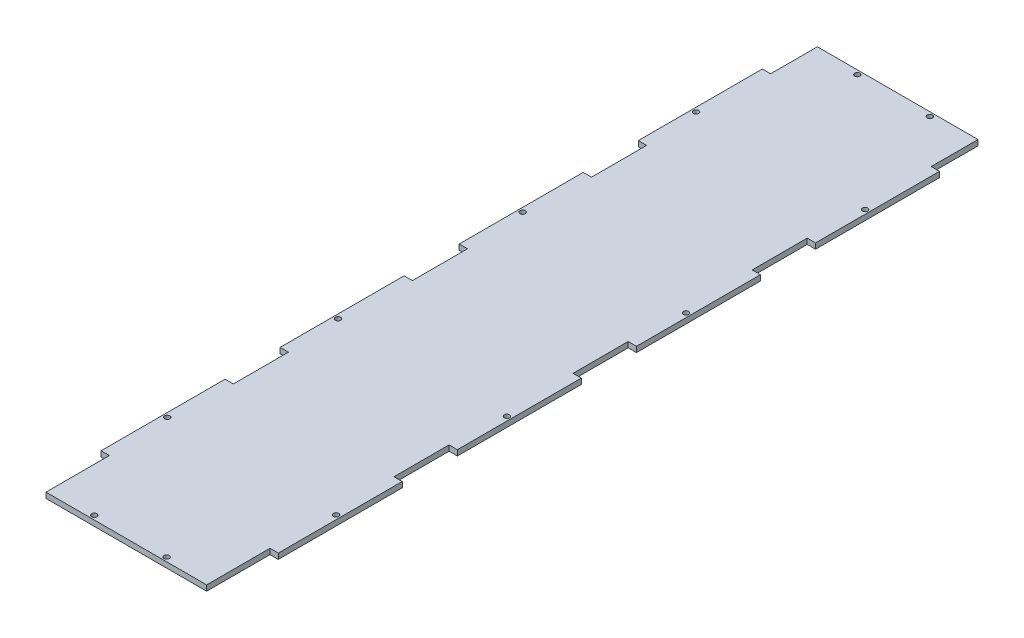
SolidWorks part; units mm, degrees
ref_plane "Front Plane" through (0, 0, 0) normal (0, 0, 1) x (1, 0, 0)
ref_plane "Top Plane" through (0, 0, 0) normal (0, 1, 0) x (1, 0, 0)
ref_plane "Right Plane" through (0, 0, 0) normal (1, 0, 0) x (0, 0, -1)
sketch "Sketch1" plane through (0, 0, 0) normal (0, 1, 0) x (1, 0, 0)
  line L0 (46.2788, 0) -> (-46.2788, 0)
  line L1 (-46.2788, 0) -> (-46.2788, 36.5125)
  line L2 (-46.2788, 36.5125) -> (-51.054, 36.5125)
  line L3 (-51.054, 36.5125) -> (-51.054, 107.95)
  line L4 (-51.054, 107.95) -> (-46.2788, 107.95)
  line L5 (-46.2788, 417.5125) -> (-46.2788, 444.4873)
  line L6 (-46.2788, 444.4873) -> (46.2788, 444.4873)
  line L7 (51.054, 417.5125) -> (46.2788, 417.5125)
  line L8 (51.054, 346.075) -> (51.054, 417.5125)
  line L9 (46.2788, 346.075) -> (51.054, 346.075)
  line L10 (46.2788, 314.325) -> (46.2788, 346.075)
  line L11 (51.054, 314.325) -> (46.2788, 314.325)
  line L12 (51.054, 242.8875) -> (51.054, 314.325)
  line L13 (46.2788, 242.8875) -> (51.054, 242.8875)
  line L14 (46.2788, 211.1375) -> (46.2788, 242.8875)
  line L15 (0, -1018.7277) -> (0, 48981.2723) construction
  line L16 (51.054, 211.1375) -> (46.2788, 211.1375)
  line L17 (51.054, 139.7) -> (51.054, 211.1375)
  line L18 (-46.2788, 107.95) -> (-46.2788, 139.7)
  line L19 (-46.2788, 139.7) -> (-51.054, 139.7)
  line L20 (-51.054, 139.7) -> (-51.054, 211.1375)
  line L21 (-51.054, 211.1375) -> (-46.2788, 211.1375)
  line L22 (-46.2788, 211.1375) -> (-46.2788, 242.8875)
  line L23 (-46.2788, 242.8875) -> (-51.054, 242.8875)
  line L24 (-51.054, 242.8875) -> (-51.054, 314.325)
  line L25 (-51.054, 314.325) -> (-46.2788, 314.325)
  line L26 (-46.2788, 314.325) -> (-46.2788, 346.075)
  line L27 (-46.2788, 346.075) -> (-51.054, 346.075)
  line L28 (-51.054, 346.075) -> (-51.054, 417.5125)
  line L29 (-51.054, 417.5125) -> (-46.2788, 417.5125)
  line L30 (46.2788, 139.7) -> (51.054, 139.7)
  line L31 (46.2788, 107.95) -> (46.2788, 139.7)
  line L32 (46.2788, 417.5125) -> (46.2788, 444.4873)
  line L33 (51.054, 107.95) -> (46.2788, 107.95)
  line L34 (51.054, 36.5125) -> (51.054, 107.95)
  line L35 (46.2788, 36.5125) -> (51.054, 36.5125)
  line L36 (46.2788, 0) -> (46.2788, 36.5125)
  line L37 (-36.4192, 273.8438) -> (-14.102, 273.8438) construction
  circle A0 centre (-48.6727, 72.2313) radius 1.524
  circle A1 centre (48.6728, 377.0313) radius 1.524
  circle A2 centre (48.6727, 273.8438) radius 1.524
  circle A3 centre (48.6727, 170.6562) radius 1.524
  circle A4 centre (-48.6728, 170.6562) radius 1.524
  circle A5 centre (-48.6728, 277.0187) radius 1.524
  circle A6 centre (-48.6728, 377.0313) radius 1.524
  circle A7 centre (48.6727, 72.2313) radius 1.524
  circle A8 centre (-20.8788, 442.1061) radius 1.524
  circle A9 centre (20.8788, 442.1061) radius 1.524
  circle A10 centre (-20.8788, 2.3812) radius 1.524
  circle A11 centre (20.8788, 2.3812) radius 1.524
  point P2 (-51.054, 72.2313)
  point P42 (0, 444.4873)
  point P57 (0, 0)
  dimension "D6" = 3.048
  dimension "D9" = 3.048
  dimension "D10" = 25.4
  dimension "D14" = 3.048
  dimension "D1" = 36.5125
  dimension "D2" = 71.4375
  dimension "D3" = 4.7752
  dimension "D4" = 46.2788
  dimension "D5" = 2.3813
  dimension "D8" = 26.9748
  dimension "D7" = 3.175
  dimension "D11" = 2.3812
  dimension "D12" = 2.3813
  dimension "D13" = 25.4
extrude "Boss-Extrude1" add sketch "Sketch1" along normal blind 3.175
